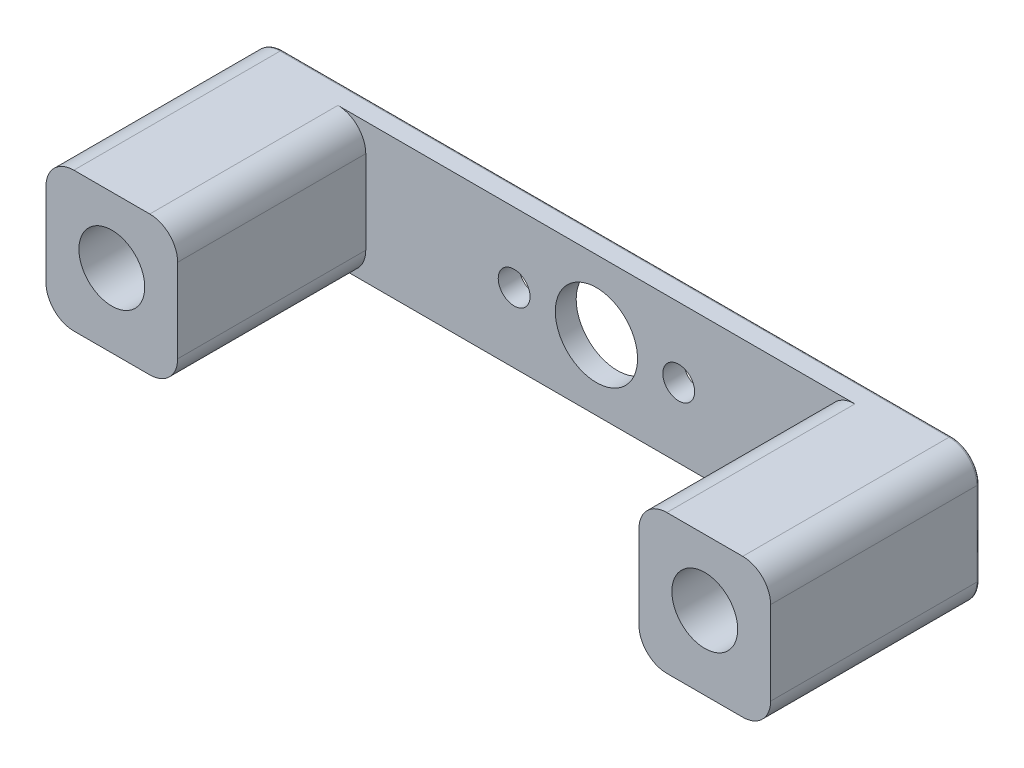
SolidWorks part; units mm, degrees
ref_plane "Front Plane" through (0, 0, 0) normal (0, 0, 1) x (1, 0, 0)
ref_plane "Top Plane" through (0, 0, 0) normal (0, 1, 0) x (1, 0, 0)
ref_plane "Right Plane" through (0, 0, 0) normal (1, 0, 0) x (0, 0, -1)
sketch "Sketch1" plane through (0, 0, 0) normal (0, 0, 1) x (1, 0, 0)
  line L1 (-33.02, 6.35) -> (33.02, 6.35)
  line L2 (-33.02, 6.35) -> (-33.02, -6.35)
  line L3 (-33.02, -6.35) -> (33.02, -6.35)
  line L4 (33.02, 6.35) -> (33.02, -6.35)
  line L5 (-33.02, 6.35) -> (33.02, -6.35) construction
  line L6 (-33.02, -6.35) -> (33.02, 6.35) construction
  line L7 (-33.02, -6.35) -> (33.02, -6.35)
  line L11 (0, -6.35) -> (0, 6.35) construction
  circle A0 centre (0, 0) radius 4.7625
  circle A1 centre (-27.0205, 0.3505) radius 2.9997
  circle A3 centre (27.0205, 0.3505) radius 2.9997
  point P0 (0, 0)
  dimension "D3" = 9.525
  dimension "D4" = 5.9995
  dimension "D1" = 12.7
  dimension "D2" = 66.04
  dimension "D5" = 5.9995
  dimension "D6" = 5.9995
extrude "Boss-Extrude1" add sketch "Sketch1" along normal blind 19.05
sketch "Sketch2" plane through (0, 0, 0) normal (0, 0, -1) x (-1, 0, 0)
  line L0 (0, 7.5) -> (0, -7.5)
  line L1 (-7.5, 0) -> (7.5, 0)
  circle A0 centre (-7.5, 0) radius 1.45
  circle A1 centre (0, -7.5) radius 1.45
  circle A2 centre (7.5, 0) radius 1.45
  circle A3 centre (0, 0) radius 3.75
  circle A4 centre (0, 7.5) radius 1.45
  point P11 (0, 0)
  point P12 (0, 0)
  dimension "D3" = 2.9
  dimension "D4" = 2.9
  dimension "D5" = 2.9
  dimension "D6" = 2.9
  dimension "D7" = 7.5
  dimension "D1" = 15
  dimension "D2" = 15
extrude "Cut-Extrude1" cut sketch "Sketch2" against normal up to surface (19.05 mm away) contours L1 A3 L0 | L0 A3 L1 | L1 A3 L0 | L0 A3 L1 | A2 | A0 region at (-7.5, 1.409, 0) region at (8.909, 0, 0) region at (-1.5915, 1.5915, 0) region at (1.5915, 1.5915, 0) region at (-1.5915, -1.5915, 0) region at (1.5915, -1.5915, 0) up to face at (0, 0, 19.05)
sketch "Sketch3" plane through (0, 6.35, 0) normal (0, 1, 0) x (1, 0, 0)
  line L0 (30.0203, 0) -> (24.0208, 0) construction
  line L1 (-24.0208, 0) -> (-30.0203, 0) construction
  line L5 (30.0203, 0) -> (24.0208, 0)
  line L6 (-24.0208, 0) -> (-30.0203, 0)
  line L8 (21.021, 0) -> (-21.021, 0)
  line L10 (21.021, -1.905) -> (-21.021, -1.905)
  line L11 (21.021, -19.05) -> (-21.021, -19.05)
  line L13 (-24.0208, 0) -> (-24.0208, -19.05) construction
  line L14 (24.0208, 0) -> (24.0208, -19.05) construction
  line L15 (21.021, 0) -> (21.021, -19.05)
  line L16 (-21.021, 0) -> (-21.021, -19.05)
  line M6 (-33.02, -19.05) -> (33.02, -19.05)
  dimension "D1" = 2.9997
  dimension "D3" = 1.905
  dimension "D2" = 2.9997
extrude "Cut-Extrude2" cut sketch "Sketch3" against normal up to surface (12.7 mm away) contours L10 L16 L15 M6 region at (0, 6.35, 10.4775) up to face at (0, -6.35, 9.525)
fillet "Fillet1" radius 2.54 8 edges at (33.02, -6.35, 9.525) (-33.02, -6.35, 9.525) (-21.021, -6.35, 10.4775) (21.021, -6.35, 10.4775) (21.021, 6.35, 10.4775) (-21.021, 6.35, 10.4775) (33.02, 6.35, 9.525) (-33.02, 6.35, 9.525)
fillet "Fillet3" radius 0.254 8 edges at (-32.2761, 5.6061, 0) (-33.02, 0, 0) (-32.2761, -5.6061, 0) (0, -6.35, 0) (32.2761, -5.6061, 0) (33.02, 0, 0) (32.2761, 5.6061, 0) (0, 6.35, 0)
